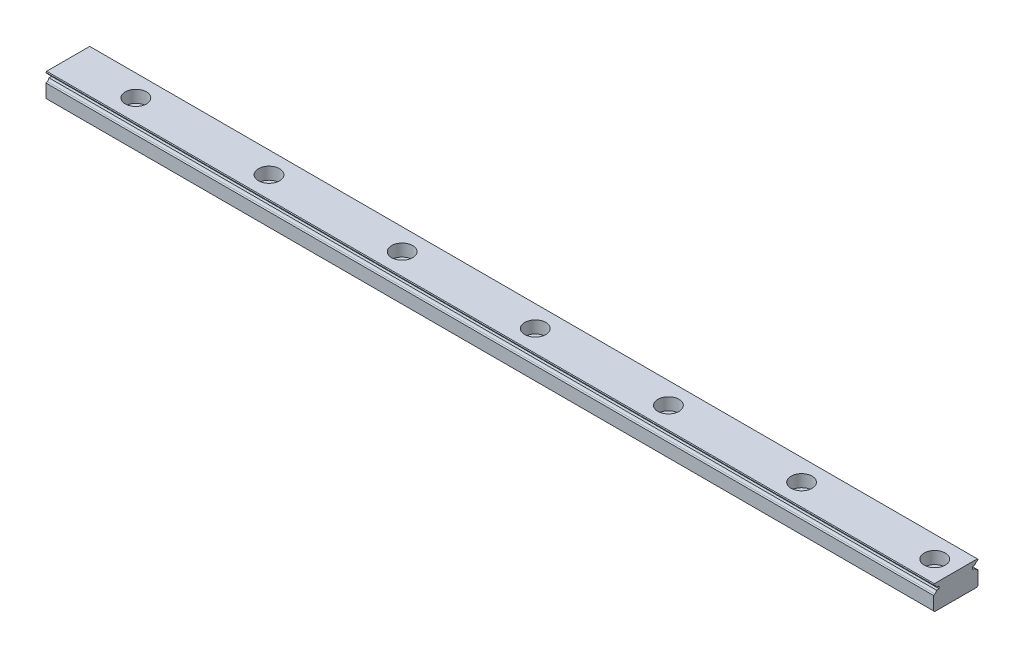
SolidWorks part; units mm, degrees
note: '?' marks a value the reader was unsure of.
ref_plane "Front Plane" through (0, 0, 0) normal (0, 0, 1) x (1, 0, 0)
ref_plane "Top Plane" through (0, 0, 0) normal (0, 1, 0) x (1, 0, 0)
ref_plane "Right Plane" through (0, 0, 0) normal (1, 0, 0) x (0, 0, -1)
ref_axis "Axis_X" through (-9.25, 0, 0) along (1, 0, 0)?
ref_plane "Dim.MC" through (4, 0, 0) normal (1, 0, 0) x (0, 0, -1)
ref_plane "Plane1" through (-30.5, 0, 0) normal (1, 0, 0) x (0, 0, -1)
sketch "Sketch1" plane through (-30.5, 0, 0) normal (1, 0, 0) x (0, 0, -1)
  line L0 (0, 11) -> (0, 0) construction
  line L1 (-10, 11) -> (10, 11)
  line L3 (-10, 0) -> (10, 0)
  line L10 (10, 11) -> (10, 0)
  line L11 (-10, 11) -> (-10, 0)
  dimension "H1" = 11
  dimension "W1" = 20
extrude "Boss-Extrude1" add sketch "Sketch1" along normal blind 400
sketch "Sketch2" plane through (-30.5, 0, 0) normal (1, 0, 0) x (0, 0, -1)
  line L0 (7.5, 8.5) -> (10, 8.5) construction
  line L1 (0, 0) -> (0, 9.1) construction
  line L2 (10, 10.451) -> (9.4553, 10.1414)
  line L3 (7.5, 9.1) -> (8.6371, 9.1)
  line L4 (7.5, 9.1) -> (7.5, 7.9)
  line L5 (7.5, 7.9) -> (8.64, 7.9)
  line L6 (9.4348, 6.8804) -> (10, 6.549)
  line L7 (0, 11) -> (0, 0) construction
  line L8 (10, 10.451) -> (10, 6.549)
  line L9 (10, 11) -> (10, 0) construction
  line L10 (-10, 0) -> (10, 0) construction
  line L11 (-7.5, 8.5) -> (-10, 8.5) construction
  line L12 (-10, 10.451) -> (-10, 6.549)
  line L13 (-9.4348, 6.8804) -> (-10, 6.549)
  line L14 (-7.5, 7.9) -> (-8.64, 7.9)
  line L15 (-7.5, 9.1) -> (-7.5, 7.9)
  line L16 (-7.5, 9.1) -> (-8.6371, 9.1)
  line L17 (-10, 10.451) -> (-9.4553, 10.1414)
  arc A0 (9.4553, 10.1414) -> (8.6371, 9.1) centre (10.32, 8.62) ccw
  arc A1 (8.64, 7.9) -> (9.4348, 6.8804) centre (10.32, 8.39) ccw
  arc A2 (-8.64, 7.9) -> (-9.4348, 6.8804) centre (-10.32, 8.39) cw
  arc A3 (-9.4553, 10.1414) -> (-8.6371, 9.1) centre (-10.32, 8.62) cw
  dimension "MSM_8" = 1.75
  dimension "MSM_6" = 8.5
  dimension "MSM_7" = 60
  dimension "MSM_2" = 0.32
  dimension "MSM_5" = 1.2
  dimension "MSM_1" = 2.5
  dimension "MSM_3" = 8.39
  dimension "MSM_4" = 8.62
extrude "Cut-Extrude1" [suppressed] cut sketch "Sketch2" along normal through all
sketch "Sketch3" plane through (-30.5, 0, 0) normal (1, 0, 0) x (0, 0, -1)
  line L0 (7.5, 8.5) -> (10, 8.5) construction
  line L1 (0, 0) -> (0, 9.1) construction
  line L2 (10, 10.451) -> (9.4553, 10.1414)
  line L3 (7.5, 9.1) -> (8.6371, 9.1)
  line L4 (7.5, 9.1) -> (7.5, 7.9)
  line L5 (7.5, 7.9) -> (8.64, 7.9)
  line L6 (10, 6.549) -> (9.4348, 6.8804)
  line L7 (10, 11) -> (10, 0) construction
  line L8 (10, 10.451) -> (10, 6.549)
  line L9 (-10, 0) -> (10, 0) construction
  line L10 (-7.5, 8.5) -> (-10, 8.5) construction
  line L11 (-10, 10.451) -> (-10, 6.549)
  line L12 (-10, 6.549) -> (-9.4348, 6.8804)
  line L13 (-7.5, 7.9) -> (-8.64, 7.9)
  line L14 (-7.5, 9.1) -> (-7.5, 7.9)
  line L15 (-7.5, 9.1) -> (-8.6371, 9.1)
  line L16 (-10, 10.451) -> (-9.4553, 10.1414)
  arc A0 (9.4553, 10.1414) -> (8.6371, 9.1) centre (10.32, 8.62) ccw
  arc A1 (8.64, 7.9) -> (9.4348, 6.8804) centre (10.32, 8.39) ccw
  arc A2 (-8.64, 7.9) -> (-9.4348, 6.8804) centre (-10.32, 8.39) cw
  arc A3 (-9.4553, 10.1414) -> (-8.6371, 9.1) centre (-10.32, 8.62) cw
  dimension "MSM_8" = 1.75
  dimension "MSM_6" = 8.5
  dimension "MSM_7" = 60
  dimension "MSM_2" = 0.32
  dimension "MSM_5" = 1.2
  dimension "MSM_1" = 2.5
  dimension "MSM_3" = 8.39
  dimension "MSM_4" = 8.62
extrude "Cut-Extrude2" cut sketch "Sketch3" along normal through all
hole_wizard "CBORE for Socket Head Cap Screw1" positions "Sketch5" profile "Sketch4" counterbore size "M3" standard "JIS" end condition through all
sketch "Sketch5" plane through (0, 11, 0) normal (0, 1, 0) x (1, 0, 0)
  line L0 (-30.5, -3.025) -> (-30.5, 3.025) construction
  point P0 (0, 0)
  dimension "G" = 30.5
sketch "Sketch4" plane through (0, 11, 0) normal (1, 0, 0) x (0, 0, 1)
  line L0 (0, 0) -> (0, 11)
  line L1 (0, 11) -> (3, 11)
  line L3 (3, 11) -> (3, 5.5)
  line L4 (3, 5.5) -> (4.75, 5.5)
  line L5 (4.75, 5.5) -> (4.75, 0)
  line L7 (4.75, 0) -> (0, 0)
  line L11 (0, 0) -> (0, 11) construction
  dimension "D1_s" = 6
  dimension "Thru Hole Depth" = 11
  dimension "D2_s" = 9.5
  dimension "H_s" = 5.5
pattern_linear "LPattern1" count 7 spacing 60 along (1, 0, 0) of "CBORE for Socket Head Cap Screw1"
chamfer "Chamfer1" distance 0.3 2 edges at (169.5, 11, 10) (169.5, 11, -10)
chamfer "Chamfer2" distance 0.5 2 edges at (169.5, 0, -10) (169.5, 0, 10)
ref_plane "Plane2" [suppressed] through (0, 5.5, 0) normal (0, 1, 0) x (1, 0, 0)
hole_wizard "Tap1" [suppressed] positions "Sketch7" profile "Sketch6" hole size "M3x0.5" standard "JIS"
sketch "Sketch7" [suppressed] plane through (0, 5.5, 0) normal (0, 1, 0) x (1, 0, 0)
  line L0 (-7.5, -3.025) -> (-7.5, 3.025) construction
  point P0 (0, 0)
  dimension "G" = 30.5
sketch "Sketch6" [suppressed] plane through (0, 5.5, 0) normal (1, 0, 0) x (0, 0, 1)
  line L0 (0, 0) -> (0, 5.5)
  line L1 (0, 5.5) -> (1.621, 5.5)
  line L2 (1.621, 5.5) -> (1.621, 0)
  line L5 (1.621, 0) -> (0, 0)
  line L11 (0, 0) -> (0, 5.5) construction
  dimension "STD_1" = 3.242
  dimension "Thru Hole Depth" = 5.5
pattern_linear "LPattern2" [suppressed]
sketch "Sketch8" [suppressed] plane through (0, 0, 0) normal (0, 0, 1) x (1, 0, 0)
  line L0 (-7.5, -3.025) -> (-7.5, 3.025) construction
  line L1 (-7.5, 5.5) -> (-5, 5.5)
  line L2 (-7.5, 5.5) -> (-7.5, 0)
  line L3 (-7.5, 0) -> (-5, 0)
  line L4 (-5, 5.5) -> (-5, 0)
  line L5 (0, 5.5) -> (0, 0) construction
  dimension "LLC" = 2.5
  dimension "N" = 5
other "Move Face1" [suppressed]
sketch "Sketch9" [suppressed] plane through (0, 0, 0) normal (0, 0, 1) x (1, 0, 0)
  line L0 (-7.5, 5.5) -> (-7.5, 0) construction
  line L1 (25, 5.5) -> (27.5, 5.5)
  line L2 (25, 5.5) -> (25, 0)
  line L3 (25, 0) -> (27.5, 0)
  line L4 (27.5, 5.5) -> (27.5, 0)
  line L5 (-7.5, -3.025) -> (-7.5, 3.025) construction
  line L8 (20, 5.5) -> (20, 0) construction
  dimension "L" = 661
  dimension "RLC" = 2.5
  dimension "N" = 5
  dimension "KSS_1" = 360
other "Move Face2" [suppressed]
equation "\"KSS_1\"= \"F\" * ( \"M\" - 1 )"
